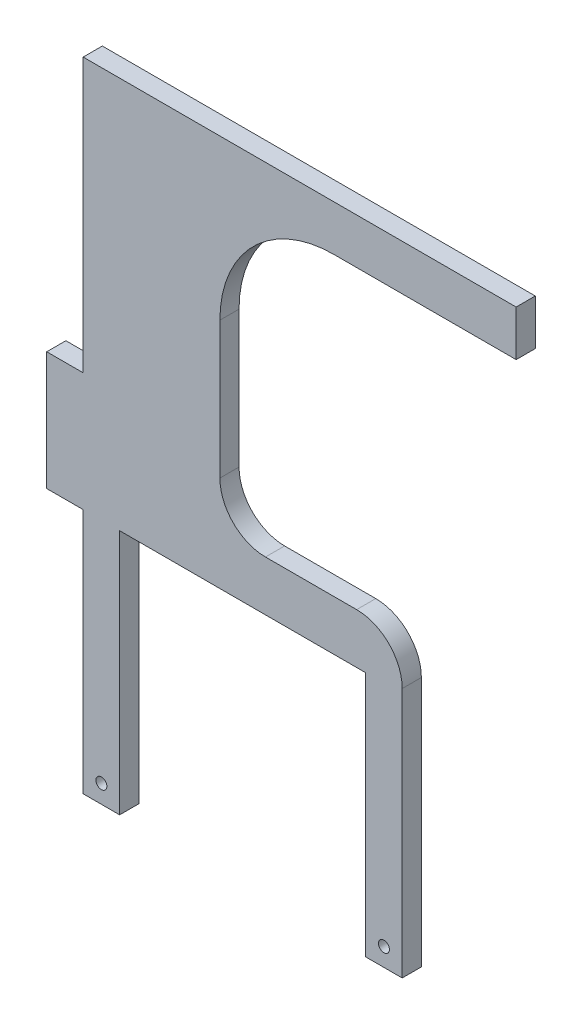
SolidWorks part; units mm, degrees
ref_plane "Plan de face" through (0, 0, 0) normal (0, 0, 1) x (1, 0, 0)
ref_plane "Plan de dessus" through (0, 0, 0) normal (0, 1, 0) x (1, 0, 0)
ref_plane "Plan de droite" through (0, 0, 0) normal (1, 0, 0) x (0, 0, -1)
sketch "Esquisse1" plane through (0, 0, 0) normal (0, 0, 1) x (1, 0, 0)
  line L36 (0, 0) -> (0, 54)
  line L41 (0, 140) -> (120, 140)
  line L42 (120, 140) -> (120, 130)
  line L43 (120, 130) -> (30, 130)
  line L44 (30, 130) -> (30, 80)
  line L45 (30, 80) -> (70, 80)
  line L46 (70, 80) -> (70, 0)
  line L47 (70, 0) -> (62, 0)
  line L48 (62, 0) -> (62, 54)
  line L49 (62, 54) -> (8, 54)
  line L50 (0, 0) -> (8, 0)
  line L51 (8, 0) -> (8, 54)
  line L52 (0, 80) -> (-8, 80)
  line L53 (-8, 80) -> (-8, 54)
  line L54 (-8, 54) -> (0, 54)
  line L55 (0, 80) -> (0, 140)
  dimension "D2" = 8
  dimension "D3" = 54
  dimension "D4" = 8
  dimension "D5" = 10
  dimension "D6" = 140
  dimension "D7" = 8
  dimension "D8" = 120
  dimension "D10" = 90
  dimension "D11" = 50
  dimension "D12" = 54
extrude "Boss.-Extru.1" add sketch "Esquisse1" along normal blind 4.2
sketch "Esquisse2" plane through (0, 0, 4.2) normal (0, 0, 1) x (1, 0, 0)
  line L0 (0, 0) -> (8, 0) construction
  line L1 (8, 0) -> (8, 54) construction
  line L2 (62, 0) -> (70, 0) construction
  line L3 (70, 0) -> (70, 80) construction
  circle A0 centre (4, 4) radius 1
  circle A1 centre (66, 4) radius 1
  dimension "D1" = 4
  dimension "D3" = 2
  dimension "D6" = 2
  dimension "D2" = 4
  dimension "D4" = 4
  dimension "D5" = 4
fillet "Congé1" [suppressed] radius 10
fillet "Congé2" radius 25 1 edges at (30, 130, 2.1)
sketch "Esquisse5" plane through (0, 0, 4.2) normal (0, 0, 1) x (1, 0, 0)
  line L0 (70, 80) -> (30, 80) construction
  line L1 (70, 80) -> (30, 80)
  line L2 (70, 80) -> (70, 65)
  line L3 (70, 65) -> (30, 65)
  line L4 (30, 80) -> (30, 65)
  line L5 (30, 80) -> (30, 105) construction
  dimension "D2" = 15
extrude "Enlèv. mat.-Extru.1" cut sketch "Esquisse5" against normal up to surface (4.2 mm away) up to face at (36.1072, 69.7752, 0)
sketch "Esquisse6" plane through (0, 0, 4.2) normal (0, 0, 1) x (1, 0, 0)
  line L0 (55, 130) -> (120, 130) construction
  line L1 (120, 140) -> (112, 140)
  line L2 (120, 140) -> (120, 130)
  line L3 (120, 130) -> (112, 130)
  line L4 (112, 140) -> (112, 130)
  dimension "D1" = 8
extrude "Enlèv. mat.-Extru.2" [suppressed] cut sketch "Esquisse6" against normal up to surface (5 mm away) up to face at (36.1072, 68.0105, 0)
fillet "Congé3" radius 10 2 edges at (70, 65, 2.1) (30, 65, 2.1)
fillet "Congé4" [suppressed] radius 10
sketch "Esquisse7" plane through (0, 0, 4.2) normal (0, 0, 1) x (1, 0, 0)
  line L0 (0, 54) -> (0, 0) construction
  line L1 (120, 140) -> (0, 140)
  line L2 (120, 140) -> (120, 80)
  line L3 (120, 80) -> (0, 80)
  line L4 (0, 140) -> (0, 80)
  line L6 (0, 80) -> (-8, 80) construction
extrude "Enlèv. mat.-Extru.3" [suppressed] cut sketch "Esquisse7" against normal up to surface (5 mm away) up to face at (37.5696, 67.6936, 0)
sketch "Esquisse8" [suppressed] plane through (0, 0, 5) normal (0, 0, 1) x (1, 0, 0)
  line L5 (0, 80) -> (-15, 80)
  line L6 (-15, 80) -> (-15, 54)
  line L7 (-15, 54) -> (0, 54)
  line L8 (0, 80) -> (0, 0) construction
  line L9 (8, 54) -> (62, 54) construction
  line L10 (0, 80) -> (0, 54)
  line L18 (45, 80) -> (0, 80)
  line L19 (0, 80) -> (0, 0)
  line L20 (0, 0) -> (8, 0)
  line L21 (8, 0) -> (8, 54)
  line L22 (8, 54) -> (62, 54)
  line L23 (62, 54) -> (62, 0)
  line L24 (62, 0) -> (70, 0)
  line L25 (70, 0) -> (70, 60)
  line L26 (45, 80) -> (0, 80)
  line L27 (0, 54) -> (0, 0)
  line L28 (0, 0) -> (8, 0)
  line L29 (8, 0) -> (8, 54)
  line L30 (8, 54) -> (62, 54)
  line L31 (62, 54) -> (62, 0)
  line L32 (62, 0) -> (70, 0)
  line L33 (70, 0) -> (70, 60)
  arc A3 (70, 60) -> (61.2017, 69.9275) centre (60, 60) ccw
  arc A4 (53.7017, 74.9275) -> (61.2017, 69.9275) centre (62.4034, 79.8551) ccw
  arc A5 (53.7017, 74.9275) -> (45, 80) centre (45, 70) ccw
  arc A6 (70, 60) -> (61.2017, 69.9275) centre (60, 60) ccw
  arc A7 (53.7017, 74.9275) -> (61.2017, 69.9275) centre (62.4034, 79.8551) ccw
  arc A8 (53.7017, 74.9275) -> (45, 80) centre (45, 70) ccw
  dimension "D1" = 15
  dimension "D2" = 0
extrude "Enlèv. mat.-Extru.5" cut sketch "Esquisse2" against normal blind 10
hole_wizard "Dégagement M21" positions "Esquisse3" profile "Esquisse4" hole size "M2" standard "ISO" end condition through all
sketch "Esquisse3" plane through (0, 0, 4.2) normal (0, 0, 1) x (1, 0, 0)
  point P0 (4, 4)
  point P3 (66, 4)
sketch "Esquisse4" plane through (4, 4, 4.2) normal (1, 0, 0) x (0, -1, 0)
  line L0 (0, 0) -> (0, 4.2)
  line L1 (0, 4.2) -> (1.2, 4.2)
  line L2 (1.2, 4.2) -> (1.2, 0)
  line L5 (1.2, 0) -> (0, 0)
  line L11 (0, -6.35) -> (0, 107.95) construction
  dimension "Diamètre du perçage jusqu'au prochain" = 2.4
  dimension "Profondeur du perçage jusqu'au prochain" = 4.2
sketch "Esquisse9" plane through (0, 0, 4.2) normal (0, 0, 1) x (1, 0, 0)
  line L0 (120, 140) -> (0, 140) construction
  line L1 (120, 130) -> (95, 130)
  line L2 (120, 130) -> (120, 140)
  line L3 (120, 140) -> (95, 140)
  line L4 (95, 130) -> (95, 140)
  dimension "D1" = 25
extrude "Enlèv. mat.-Extru.6" cut sketch "Esquisse9" against normal up to surface (4.2 mm away) up to face at (5.2, 4, 0)
